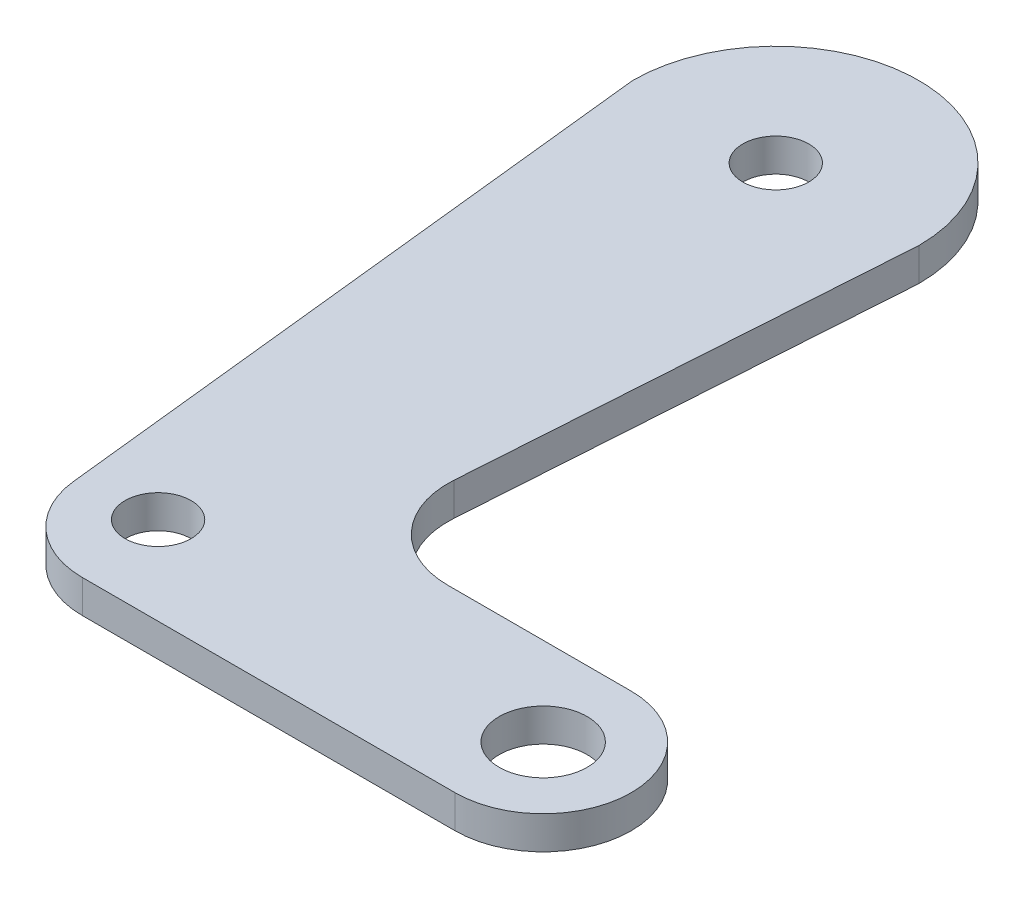
SolidWorks part; units mm, degrees
ref_plane "Piano frontale" through (0, 0, 0) normal (0, 0, 1) x (1, 0, 0)
ref_plane "Piano superiore" through (0, 0, 0) normal (0, 1, 0) x (1, 0, 0)
ref_plane "Piano destro" through (0, 0, 0) normal (1, 0, 0) x (0, 0, -1)
sketch "Schizzo1" plane through (0, 0, 0) normal (0, 1, 0) x (1, 0, 0)
  line L0 (35, -8) -> (1.1086, -8)
  line L1 (-6.8451, -0.8588) -> (-13, 56.1412)
  line L2 (13, 56.1412) -> (10.3436, 16.5354)
  line L3 (18.3257, 8) -> (35, 8)
  circle A0 centre (0, 0) radius 3
  circle A1 centre (35, 0) radius 4
  circle A2 centre (0, 56.1412) radius 3
  arc A3 (13, 56.1412) -> (-13, 56.1412) centre (0, 56.1412) ccw
  arc A4 (35, -8) -> (35, 8) centre (35, 0) ccw
  arc A5 (10.3436, 16.5354) -> (18.3257, 8) centre (18.3257, 16) ccw
  arc A6 (1.1086, -8) -> (-6.8451, -0.8588) centre (1.1086, 0) cw
  point P6 (0, 0)
  point P7 (0, 0)
  point P13 (0, 0)
  point P15 (0, 0)
  point P16 (0, 0)
  point P18 (0, 0)
  point P19 (0, 0)
  point P20 (-6.084, -8)
  dimension "D1" = 6
  dimension "D2" = 6
  dimension "D3" = 8
  dimension "D6" = 26
  dimension "D7" = 16
  dimension "D9" = 8
  dimension "D4" = 35
  dimension "D5" = 57
  dimension "D8" = 10
  dimension "D10" = 56.1412
base flange "Base-Flangia1" sketch "Schizzo1" thickness 3 reverse thickness direction no parameters "D1"=0.7366
sketch "Linee di piegatura1" [suppressed] plane through (0, 0, 0) normal (0, 1, 0) x (1, 0, 0)
sketch "Casella di contorno1" [suppressed] plane through (0, 0, 0) normal (0, 1, 0) x (1, 0, 0)
sheet metal parameters "Lamiera1" thickness 3 parameters "D1"=0.7366
flat pattern "Ripetizione piatta1" [suppressed]
sketch "Linee di piegatura2" plane through (0, 0, 0) normal (0, 1, 0) x (1, 0, 0)
sketch3d "Casella di contorno2" [suppressed]
  line L0 (70.2964, 52.3539, 0) -> (29.9959, -24.7133, 0) construction
  line L1 (29.5042, 73.6852, 0) -> (-10.7963, -3.382, 0) construction
  line L2 (70.2964, 52.3539, 0) -> (29.5042, 73.6852, 0) construction
  line L3 (29.9959, -24.7133, 0) -> (-10.7963, -3.382, 0) construction
